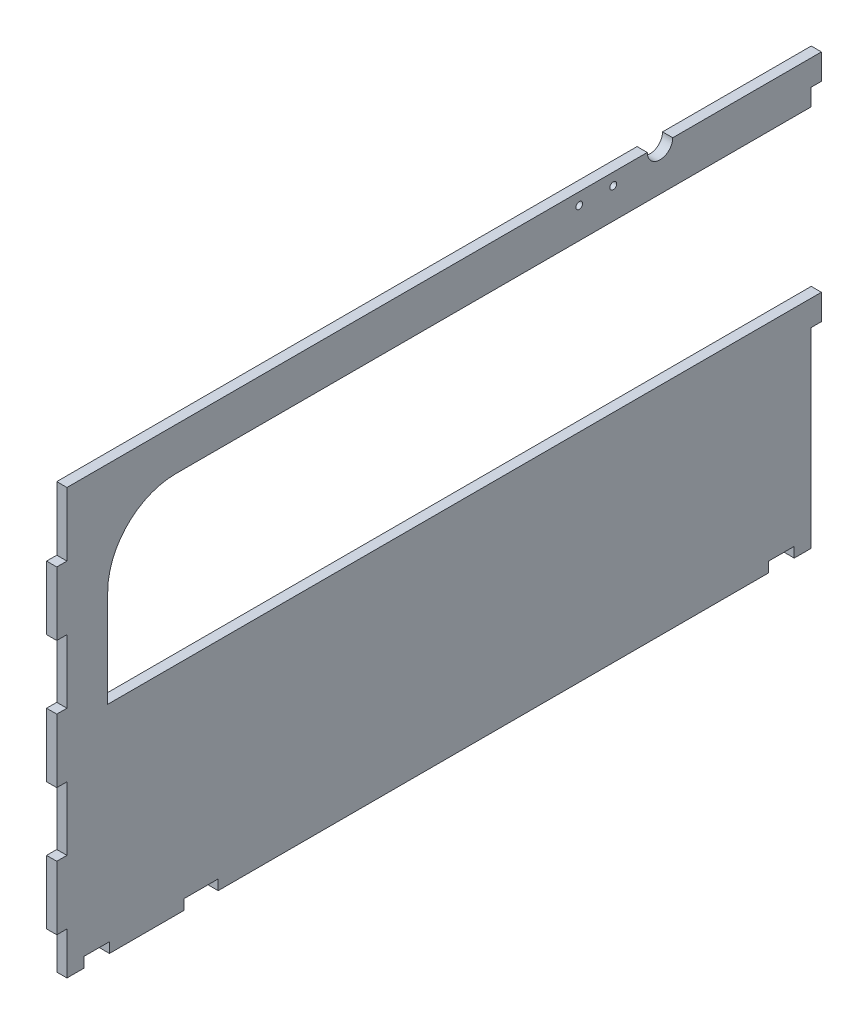
SolidWorks part; units mm, degrees
ref_plane "Front" through (0, 0, 0) normal (0, 0, 1) x (1, 0, 0)
ref_plane "Top" through (0, 0, 0) normal (0, 1, 0) x (1, 0, 0)
ref_plane "Right" through (0, 0, 0) normal (1, 0, 0) x (0, 0, -1)
sketch "Sketch1" plane through (0, 0, 0) normal (1, 0, 0) x (0, 0, -1)
  line L0 (450, 225) -> (450, 250)
  line L1 (0, 0) -> (450, 0)
  line L2 (0, 0) -> (0, 250)
  line L3 (0, 250) -> (450, 250)
  line L4 (450, 0) -> (450, 127.5)
  line L5 (450, 225) -> (30, 225)
  line L7 (450, 127.5) -> (30, 127.5)
  line L8 (30, 225) -> (30, 127.5)
  dimension "D1" = 420
  dimension "D2" = 250
  dimension "D3" = 127.5
  dimension "D4" = 25
  dimension "D5" = 30
extrude "Boss-Extrude1" add sketch "Sketch1" along normal blind 6
sketch "Sketch2" plane through (6, 0, 0) normal (1, 0, 0) x (0, 0, -1)
  line L1 (0, 250) -> (6, 250)
  line L2 (0, 250) -> (0, 212.5)
  line L3 (0, 212.5) -> (6, 212.5)
  line L4 (6, 250) -> (6, 212.5)
  dimension "D1" = 6
  dimension "D2" = 37.5
extrude "Cut-Extrude1" cut sketch "Sketch2" against normal blind 6
pattern_linear "LPattern1" count 4 spacing 75 along (0, -1, 0) of "Cut-Extrude1"
fillet "Fillet1" radius 40 1 edges at (3, 225, -30)
sketch "Sketch3" plane through (0, 0, 0) normal (-1, 0, 0) x (0, 0, 1)
  line L0 (-450, 0) -> (-450, 127.5) construction
  line L1 (-450, 235) -> (-444, 235)
  line L2 (-450, 235) -> (-450, 225)
  line L3 (-450, 225) -> (-444, 225)
  line L4 (-444, 235) -> (-444, 225)
  line L5 (-70, 225) -> (-450, 225) construction
  line L7 (-450, 112.5) -> (-444, 112.5)
  line L8 (-450, 112.5) -> (-450, 0)
  line L9 (-450, 0) -> (-444, 0)
  line L10 (-444, 112.5) -> (-444, 0)
  line L12 (-450, 225) -> (-450, 250) construction
  line L13 (-450, 127.5) -> (-30, 127.5) construction
  line L14 (-6, 0) -> (-450, 0) construction
  dimension "D1" = 6
  dimension "D2" = 10
  dimension "D4" = 15
extrude "Cut-Extrude2" cut sketch "Sketch3" against normal through all
sketch "Sketch4" plane through (0, 0, 0) normal (-1, 0, 0) x (0, 0, 1)
  line L0 (-6, 0) -> (-444, 0) construction
  line L1 (-16, 0) -> (-31, 0)
  line L2 (-16, 0) -> (-16, 6)
  line L3 (-16, 6) -> (-31, 6)
  line L4 (-31, 0) -> (-31, 6)
  line L5 (-6, 62.5) -> (-6, 100) construction
  line L6 (-6, 0) -> (-444, 0) construction
  line L7 (-434, 0) -> (-419, 0)
  line L8 (-434, 0) -> (-434, 6)
  line L9 (-434, 6) -> (-419, 6)
  line L10 (-419, 0) -> (-419, 6)
  line L11 (-444, 0) -> (-444, 112.5) construction
  dimension "D1" = 10
  dimension "D2" = 15
  dimension "D3" = 6
  dimension "D4" = 10
extrude "Cut-Extrude3" cut sketch "Sketch4" against normal through all
sketch "Sketch5" plane through (0, 0, 0) normal (-1, 0, 0) x (0, 0, 1)
  line L0 (-450, 235) -> (-450, 250) construction
  line L1 (-450, 250) -> (-6, 250) construction
  line L2 (-362.5, 250) -> (-347.5, 250)
  line L3 (-444, 235) -> (-450, 235) construction
  circle A0 centre (-327.5, 243) radius 2
  circle A1 centre (-307.5, 243) radius 2
  arc A3 (-362.5, 250) -> (-347.5, 250) centre (-355, 250) ccw
  dimension "D3" = 4
  dimension "D5" = 95
  dimension "D6" = 7.5
  dimension "D1" = 122.5
  dimension "D2" = 7
  dimension "D4" = 20
  dimension "D7" = 15
extrude "Cut-Extrude4" cut sketch "Sketch5" against normal through all
sketch "Sketch6" plane through (0, 0, 0) normal (-1, 0, 0) x (0, 0, 1)
  line L0 (-31, 0) -> (-419, 0) construction
  line L1 (-75, 0) -> (-95, 0)
  line L2 (-75, 0) -> (-75, 6)
  line L3 (-75, 6) -> (-95, 6)
  line L4 (-95, 0) -> (-95, 6)
  line L6 (-16, 6) -> (-31, 6) construction
  line L7 (0, 62.5) -> (0, 25) construction
  dimension "D1" = 20
  dimension "D2" = 75
extrude "Cut-Extrude5" cut sketch "Sketch6" against normal through all
